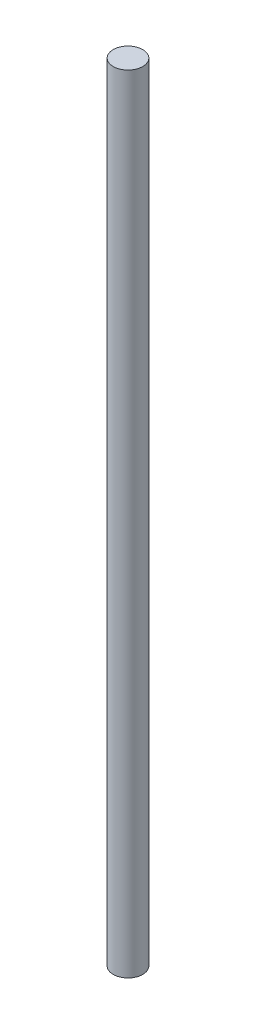
SolidWorks part; units mm, degrees
ref_plane "Front Plane" through (0, 0, 0) normal (0, 0, 1) x (1, 0, 0)
ref_plane "Top Plane" through (0, 0, 0) normal (0, 1, 0) x (1, 0, 0)
ref_plane "Right Plane" through (0, 0, 0) normal (1, 0, 0) x (0, 0, -1)
sketch "Sketch1" plane through (0, 0, 0) normal (0, 1, 0) x (1, 0, 0)
  circle A0 centre (0, 0) radius 3.75
  dimension "D1" = 7.5
extrude "Boss-Extrude1" add sketch "Sketch1" along normal blind 200
ref_axis "Axis1" through (0, 200, 0) along (0, -1, 0)
